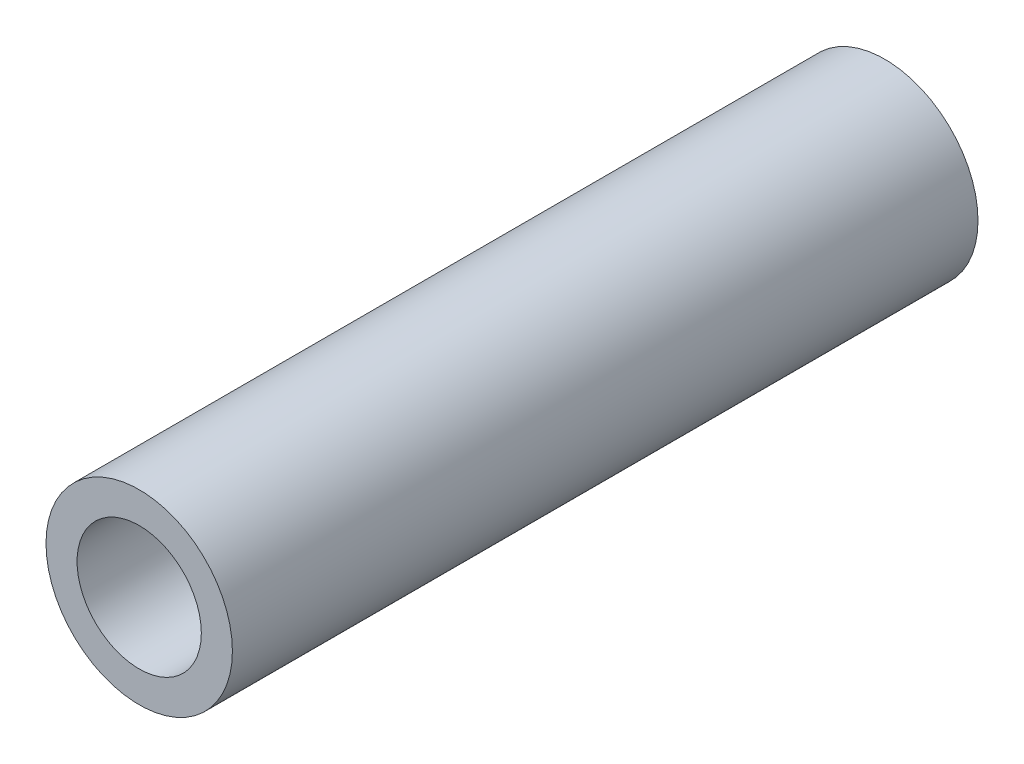
SolidWorks part; units mm, degrees
ref_plane "Front" through (0, 0, 0) normal (0, 0, 1) x (1, 0, 0)
ref_plane "Top" through (0, 0, 0) normal (0, 1, 0) x (1, 0, 0)
ref_plane "Right" through (0, 0, 0) normal (1, 0, 0) x (0, 0, -1)
other "Configuration Table"
sketch "Sketch1" plane through (0, 0, 0) normal (0, 0, 1) x (1, 0, 0)
  circle A0 centre (0, 0) radius 25.4
  circle A1 centre (0, 0) radius 38.1
  dimension "D1" = 50.8
  dimension "D2" = 76.2
extrude "Extrude1" add sketch "Sketch1" against normal blind 304.8
ref_axis "Axis1" through (0, 0, 0) along (0, 0, -1)
